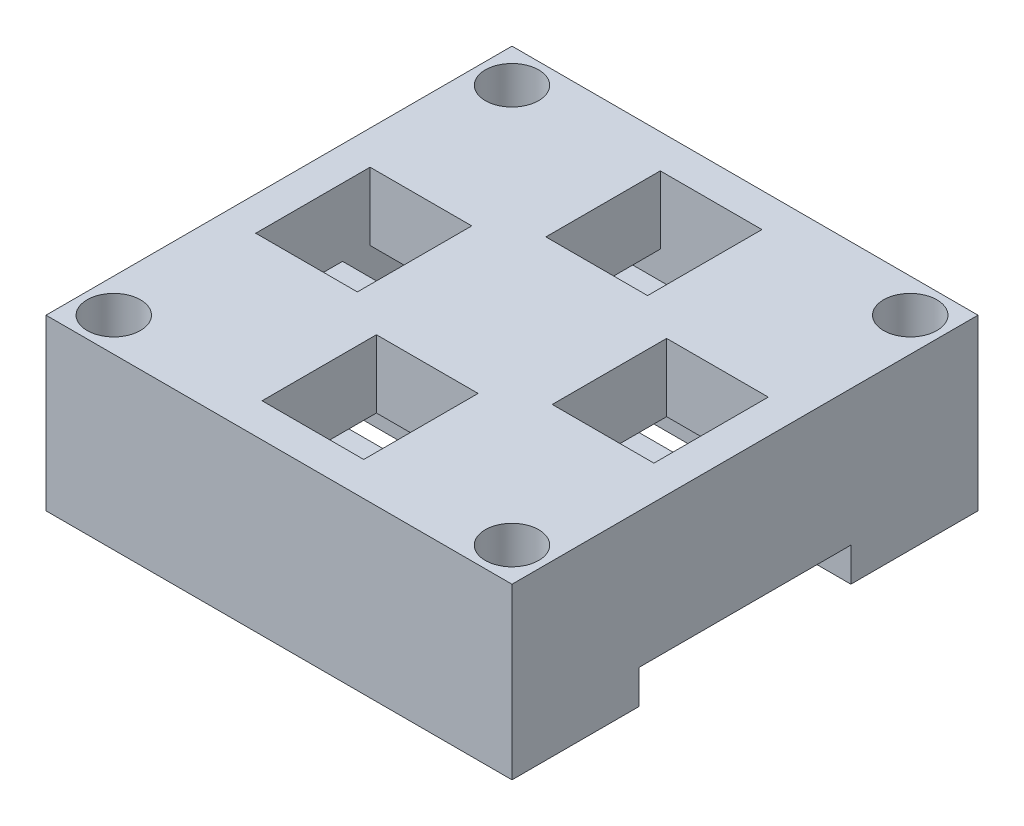
SolidWorks part; units mm, degrees
ref_plane "Front Plane" through (0, 0, 0) normal (0, 0, 1) x (1, 0, 0)
ref_plane "Top Plane" through (0, 0, 0) normal (0, 1, 0) x (1, 0, 0)
ref_plane "Right Plane" through (0, 0, 0) normal (1, 0, 0) x (0, 0, -1)
sketch "Sketch1" plane through (0, 0, 0) normal (0, 1, 0) x (1, 0, 0)
  line L1 (-27.5, 27.5) -> (27.5, 27.5)
  line L2 (-27.5, 27.5) -> (-27.5, -27.5)
  line L3 (-27.5, -27.5) -> (27.5, -27.5)
  line L4 (27.5, 27.5) -> (27.5, -27.5)
  line L5 (-27.5, 27.5) -> (27.5, -27.5) construction
  line L6 (-27.5, -27.5) -> (27.5, 27.5) construction
  line L7 (-6, 23.5) -> (6, 23.5)
  line L8 (-6, 23.5) -> (-6, 10)
  line L9 (-6, 10) -> (6, 10)
  line L10 (6, 23.5) -> (6, 10)
  line L11 (-6, 23.5) -> (6, 10) construction
  line L12 (-6, 10) -> (6, 23.5) construction
  line L13 (11.5, 6.75) -> (23.5, 6.75)
  line L14 (11.5, 6.75) -> (11.5, -6.75)
  line L15 (11.5, -6.75) -> (23.5, -6.75)
  line L16 (23.5, 6.75) -> (23.5, -6.75)
  line L17 (11.5, 6.75) -> (23.5, -6.75) construction
  line L18 (11.5, -6.75) -> (23.5, 6.75) construction
  line L19 (-23.5, 6.75) -> (-11.5, 6.75)
  line L20 (-23.5, 6.75) -> (-23.5, -6.75)
  line L21 (-23.5, -6.75) -> (-11.5, -6.75)
  line L22 (-11.5, 6.75) -> (-11.5, -6.75)
  line L23 (-23.5, 6.75) -> (-11.5, -6.75) construction
  line L24 (-23.5, -6.75) -> (-11.5, 6.75) construction
  line L25 (6, -23.5) -> (-6, -23.5)
  line L26 (6, -23.5) -> (6, -10)
  line L27 (6, -10) -> (-6, -10)
  line L28 (-6, -23.5) -> (-6, -10)
  line L29 (6, -23.5) -> (-6, -10) construction
  line L30 (6, -10) -> (-6, -23.5) construction
  point P0 (0, 0)
  point P6 (0, 16.75)
  point P11 (17.5, 0)
  point P16 (-17.5, 0)
  point P21 (0, -16.75)
  dimension "D1" = 55
  dimension "D2" = 55
  dimension "D3" = 13.5
  dimension "D4" = 12
  dimension "D5" = 12
  dimension "D6" = 13.5
  dimension "D7" = 13.5
  dimension "D8" = 12
  dimension "D9" = 13.5
  dimension "D10" = 12
  dimension "D11" = 4
  dimension "D12" = 4
  dimension "D13" = 4
  dimension "D14" = 4
  dimension "D15" = 27.5
  dimension "D16" = 27.5
  dimension "D17" = 27.5
extrude "Boss-Extrude1" add sketch "Sketch1" along normal blind 8
sketch "Sketch2" plane through (0, 0, 0) normal (0, -1, 0) x (1, 0, 0)
  line L0 (-6, 23.5) -> (-23.5, 23.5)
  line L1 (-11.9, 20.25) -> (11.7, 20.25)
  line L2 (-11.9, 20.25) -> (-11.9, 13.25)
  line L3 (-11.9, 13.25) -> (11.7, 13.25)
  line L4 (11.7, 20.25) -> (11.7, 13.25)
  line L5 (-11.9, 20.25) -> (11.7, 13.25) construction
  line L6 (-11.9, 13.25) -> (11.7, 20.25) construction
  line L12 (-23.5, 3.5) -> (23.5, 3.5)
  line L17 (-23.5, 3.5) -> (-23.5, -3.5)
  line L18 (-23.5, -3.5) -> (23.5, -3.5)
  line L19 (-11.9, -13.25) -> (11.7, -13.25)
  line L20 (-11.9, -13.25) -> (-11.9, -20.25)
  line L21 (-11.9, -20.25) -> (11.7, -20.25)
  line L22 (11.7, -13.25) -> (11.7, -20.25)
  line L23 (-11.9, -13.25) -> (11.7, -20.25) construction
  line L24 (-11.9, -20.25) -> (11.7, -13.25) construction
  line L25 (-23.5, -23.5) -> (-23.5, 23.5)
  line L26 (23.5, -23.5) -> (-23.5, -23.5)
  line L27 (-6, 23.5) -> (23.5, 23.5)
  line L28 (23.5, -23.5) -> (23.5, 23.5)
  line L31 (-6, 10) -> (-6, 23.5) construction
  line L32 (6, 10) -> (-6, 10) construction
  line L33 (-6, -23.5) -> (-6, -10) construction
  line L36 (23.5, 3.5) -> (23.5, -3.5)
  line L37 (-23.5, 3.5) -> (23.5, -3.5) construction
  line L38 (-23.5, -3.5) -> (23.5, 3.5) construction
  point P0 (-0.1, 16.75)
  point P5 (-15.2275, 0.8547)
  point P6 (0, 0)
  point P10 (14.3332, 1.7102)
  point P15 (-0.1, -16.75)
  point P40 (-6, -16.75)
  line M21 (-23.5, -6.75) -> (-23.5, 6.75)
  line M24 (6, -23.5) -> (-6, -23.5)
  line M27 (27.5, -27.5) -> (27.5, 27.5)
  line M28 (27.5, 27.5) -> (-27.5, 27.5)
  line M29 (-27.5, 27.5) -> (-27.5, -27.5)
  line M30 (-27.5, -27.5) -> (27.5, -27.5)
  line M31 (23.5, 6.75) -> (23.5, -6.75)
  line M36 (-6, 23.5) -> (6, 23.5)
  dimension "D1" = 23.6
  dimension "D2" = 7
  dimension "D1*(1/4)" = 5.8004
  dimension "D3" = 3.25
  dimension "D1/4" = 5.9
  dimension "D4" = 7
  dimension "D5" = 3.25
  dimension "D6" = 5.9
  dimension "D7" = 7
  dimension "D8" = 0
extrude "Boss-Extrude7" add sketch "Sketch2" along normal blind 12 contours L28 L26 L25 L0 L27 M30 M27 M28 M29 M24 M21 M36 M31 region at (0, 0, -26.7222)
extrude "Boss-Extrude8" add sketch "Sketch2<5>" along normal blind 8 contours L1 L4 L3 L2 | L12 L36 L18 L17 | L19 L22 L21 L20
sketch "Sketch2<5>" plane through (0, 0, 0) normal (0, -1, 0) x (1, 0, 0) same geometry as "Sketch2"
sketch "Sketch6" plane through (0, -12, 0) normal (0, -1, 0) x (1, 0, 0)
  circle A0 centre (-23.5, 23.5) radius 3.15
  circle A1 centre (23.5, 23.5) radius 3.15
  circle A2 centre (-23.5, -23.5) radius 3.15
  circle A3 centre (23.5, -23.5) radius 3.15
  dimension "D1" = 6.3
extrude "Cut-Extrude1" cut sketch "Sketch6" against normal through all
sketch "Sketch7" plane through (27.5, 0, 0) normal (1, 0, 0) x (0, 0, -1)
  line L0 (0, -12) -> (0, 8) construction
  line L1 (27.5, -12) -> (-27.5, -12) construction
  line L2 (-27.5, 8) -> (27.5, 8) construction
  line L3 (-12.4978, -12) -> (12.4978, -12)
  line L5 (-12.4978, -12) -> (-12.4978, -8)
  line L6 (-12.4978, -8) -> (12.4978, -8)
  line L7 (12.4978, -12) -> (12.4978, -8)
  line L8 (0, -12) -> (12.4978, -8) construction
  line L9 (-12.4978, -8) -> (0, -12) construction
  dimension "D1" = 4
extrude "Cut-Extrude3" cut sketch "Sketch7" against normal blind 4
